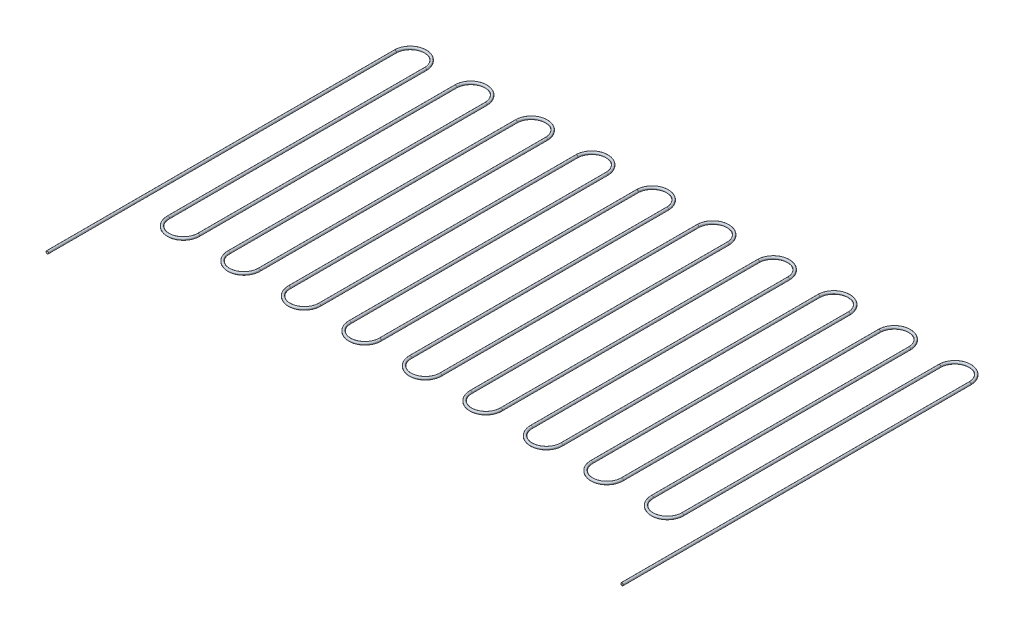
SolidWorks part; units mm, degrees
ref_plane "Front Plane" through (0, 0, 0) normal (0, 0, 1) x (1, 0, 0)
ref_plane "Top Plane" through (0, 0, 0) normal (0, 1, 0) x (1, 0, 0)
ref_plane "Right Plane" through (0, 0, 0) normal (1, 0, 0) x (0, 0, -1)
sketch "Sketch4" plane through (0, 0, 0) normal (0, 1, 0) x (1, 0, 0)
  line L0 (950, -425) -> (950, 425)
  line L5 (850, -425) -> (850, 425)
  line L6 (750, -425) -> (750, 425)
  line L7 (650, -425) -> (650, 425)
  line L8 (550, -425) -> (550, 425)
  line L9 (450, -425) -> (450, 425)
  line L10 (350, -425) -> (350, 425)
  line L11 (250, -425) -> (250, 425)
  line L12 (150, -425) -> (150, 425)
  line L13 (50, -425) -> (50, 425)
  line L14 (-50, -425) -> (-50, 425)
  line L15 (-150, -425) -> (-150, 425)
  line L16 (-250, -425) -> (-250, 425)
  line L17 (-350, -425) -> (-350, 425)
  line L18 (-450, -425) -> (-450, 425)
  line L19 (-550, -425) -> (-550, 425)
  line L20 (-650, -425) -> (-650, 425)
  line L21 (-750, -425) -> (-750, 425)
  line L22 (-850, -425) -> (-850, 425)
  line L23 (-950, -425) -> (-950, 425)
  line L24 (-950, -425) -> (-950, -725)
  line L25 (950, -425) -> (950, -725)
  line L27 (50, 0) -> (-49950, 0) construction
  arc A0 (950, 425) -> (850, 425) centre (900, 425) ccw
  arc A1 (750, 425) -> (650, 425) centre (700, 425) ccw
  arc A2 (550, 425) -> (450, 425) centre (500, 425) ccw
  arc A3 (350, 425) -> (250, 425) centre (300, 425) ccw
  arc A4 (50, 425) -> (150, 425) centre (100, 425) cw
  arc A5 (-150, 425) -> (-50, 425) centre (-100, 425) cw
  arc A6 (-350, 425) -> (-250, 425) centre (-300, 425) cw
  arc A7 (-550, 425) -> (-450, 425) centre (-500, 425) cw
  arc A8 (-650, 425) -> (-750, 425) centre (-700, 425) ccw
  arc A9 (-750, -425) -> (-850, -425) centre (-800, -425) cw
  arc A10 (-550, -425) -> (-650, -425) centre (-600, -425) cw
  arc A11 (-350, -425) -> (-450, -425) centre (-400, -425) cw
  arc A12 (-150, -425) -> (-250, -425) centre (-200, -425) cw
  arc A13 (-50, -425) -> (50, -425) centre (0, -425) ccw
  arc A14 (150, -425) -> (250, -425) centre (200, -425) ccw
  arc A15 (350, -425) -> (450, -425) centre (400, -425) ccw
  arc A16 (650, -425) -> (550, -425) centre (600, -425) cw
  arc A17 (750, -425) -> (850, -425) centre (800, -425) ccw
  arc A18 (-850, 425) -> (-950, 425) centre (-900, 425) ccw
  point P67 (50, 0)
  dimension "D8" = 300
  dimension "D6" = 100
  dimension "D4" = 850
  dimension "D3" = 20
sweep "Sweep-Thin1" add path "Sketch4" circular profile diameter 8.5 parameters "D1"=0.35, "D3"=8.5
equation "\"absorber_plate_width\" = 1000mm"
equation "\"absorber_plate_length\" = 2000mm"
equation "\"absorber_plate_thickness\" = 4mm"
equation "\"groove_depth\" = 10mm"
equation "\"frame_thickness\" = 60mm"
equation "\"insulation_thickness\" = 50mm"
equation "\"glass_thickness\" = 3mm"
equation "\"pipe_distances\" = 100mm"
equation "\"pipe_OD\" = 8.5mm"
equation "\"pipe_ID\" = 7.8mm"
equation "\"D6@Sketch4\"=\"pipe_distances\""
equation "\"D3@Sweep-Thin1\"=\"pipe_OD\""
equation "\"D4@Sketch4\"=\"absorber_plate_width\"-\"pipe_distances\"*1.5"
